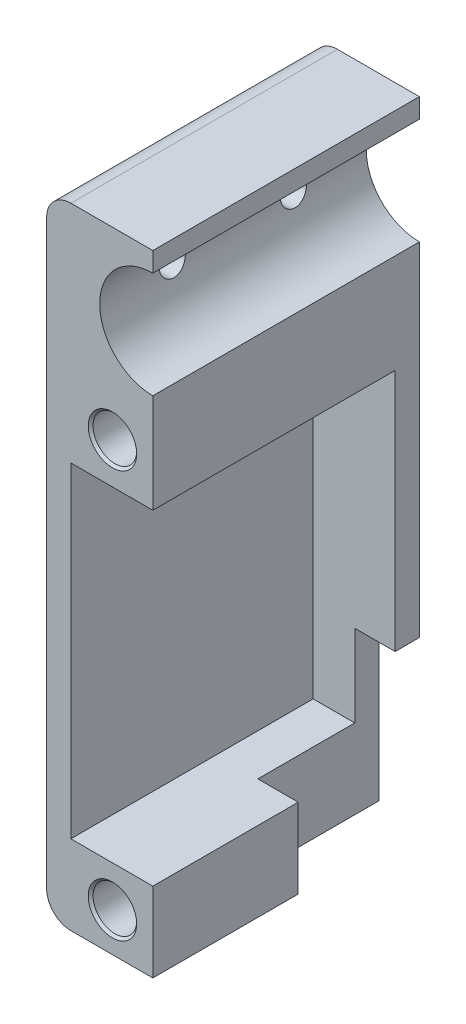
SolidWorks part; units mm, degrees
note: The reader was unsure of these and kept them because the rebuilt part matched: shared geometry of "Sketch1<2>".
ref_plane "Front Plane" through (0, 0, 0) normal (0, 0, 1) x (1, 0, 0)
ref_plane "Top Plane" through (0, 0, 0) normal (0, 1, 0) x (1, 0, 0)
ref_plane "Right Plane" through (0, 0, 0) normal (1, 0, 0) x (0, 0, -1)
sketch "Sketch1" plane through (0, 0, 0) normal (0, 0, 1) x (1, 0, 0)
  line L1 (-10.15, 20.15) -> (10.15, 20.15)
  line L2 (-10.15, 20.15) -> (-10.15, -20.15)
  line L3 (-10.15, -20.15) -> (10.15, -20.15)
  line L4 (10.15, 20.15) -> (10.15, -20.15)
  line L5 (-10.15, 20.15) -> (10.15, -20.15) construction
  line L6 (-10.15, -20.15) -> (10.15, 20.15) construction
  line L11 (-13.15, 30) -> (13.15, 30)
  line L12 (-13.15, 30) -> (-13.15, -30)
  line L13 (-13.15, -30) -> (13.15, -30)
  line L14 (13.15, 30) -> (13.15, -30)
  point P0 (0, 0)
  point P6 (0, 0)
  dimension "D1" = 40.3
  dimension "D2" = 20.3
  dimension "D3" = 3
  dimension "D4" = 60
extrude "Boss-Extrude1" add sketch "Sketch1" against normal blind 30
extrude "Boss-Extrude2" add sketch "Sketch1<2>" against normal blind 3 from surface at -30 starting at face at (0, 0, -30)
sketch "Sketch1<2>" plane through (0, 0, 0) normal (0, 0, 1) x (1, 0, 0) same geometry as "Sketch1"
sketch "Sketch2" plane through (0, 0, 0) normal (0, 0, 1) x (1, 0, 0)
  line L1 (-13.15, 30) -> (13.15, 30)
  line L2 (-13.15, 30) -> (-13.15, 48)
  line L3 (-13.15, 48) -> (13.15, 48)
  line L4 (13.15, 30) -> (13.15, 48)
  circle A0 centre (0, 39) radius 6.575
  point P8 (13.15, 39)
  dimension "D2" = 13.15
  dimension "D1" = 18
extrude "Boss-Extrude3" add sketch "Sketch2" against normal blind 33
sketch "Sketch3" plane through (0, -30, 0) normal (0, -1, 0) x (1, 0, 0)
  line L0 (-13.15, -33) -> (13.15, -33) construction
  line L1 (-5, -33) -> (5, -33)
  line L2 (-5, -33) -> (-5, -18)
  line L3 (-5, -18) -> (5, -18)
  line L4 (5, -33) -> (5, -18)
  line L6 (-13.15, -33) -> (-13.15, 0) construction
  dimension "D1" = 10
  dimension "D2" = 15
  dimension "D3" = 8.15
extrude "Cut-Extrude1" cut sketch "Sketch3" against normal blind 20
sketch "Sketch4" plane through (13.15, 0, 0) normal (1, 0, 0) x (0, 0, -1)
  line L0 (0, 39) -> (33, 39) construction
  line L1 (0, -30) -> (0, 48) construction
  line L2 (33, 48) -> (33, -30) construction
  line L3 (33, 48) -> (0, 48) construction
  line L5 (0, 33.9) -> (33, 33.9)
  line L6 (0, 33.9) -> (0, 44.1)
  line L7 (0, 44.1) -> (33, 44.1)
  line L8 (33, 33.9) -> (33, 44.1)
  circle A0 centre (9, 39) radius 1.6
  circle A1 centre (24, 39) radius 1.6
  dimension "D4" = 3.2
  dimension "D5" = 3.2
  dimension "D1" = 9
  dimension "D2" = 5.1
  dimension "D3" = 5.1
  dimension "D6" = 15
  dimension "D7" = 9
extrude "Cut-Extrude2" cut sketch "Sketch4" against normal through all contours A0 L0 | L0 A0 | A1 L0 | L0 A1
fillet "Fillet1" radius 3 4 edges at (-13.15, 48, -16.5) (13.15, 48, -16.5) (-13.15, -30, -16.5) (13.15, -30, -16.5)
ref_plane "Plane1" through (0, 0, 0) normal (-1, 0, 0) x (0, 0, 1)
other "SurfaceCut2"
sketch "Sketch5" plane through (0, 0, 0) normal (0, 0, 1) x (1, 0, 0)
  circle A0 centre (-5, -25.2) radius 2.7
  circle A1 centre (-5, 25.2) radius 2.7
  dimension "D1" = 5.4
  dimension "D2" = 5.4
extrude "Cut-Extrude4" cut sketch "Sketch5" against normal blind 4.2
chamfer "Chamfer1" distance 0.3 angle 45 2 edges at (-2.3, -25.2, 0) (-2.3, 25.2, 0)
